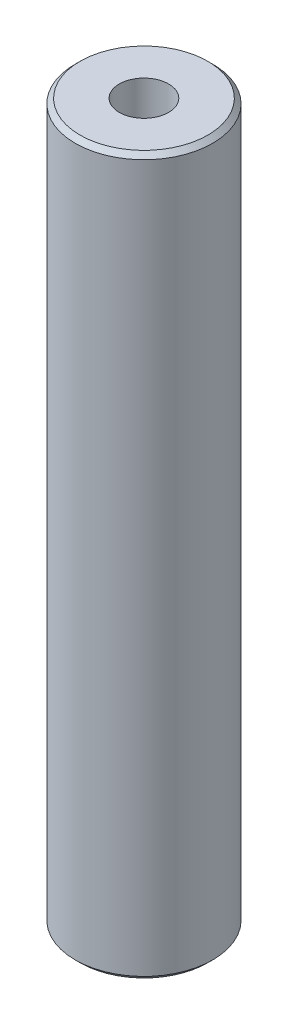
SolidWorks part; units mm, degrees
ref_plane "Front Plane" through (0, 0, 0) normal (0, 0, 1) x (1, 0, 0)
ref_plane "Top Plane" through (0, 0, 0) normal (0, 1, 0) x (1, 0, 0)
ref_plane "Right Plane" through (0, 0, 0) normal (1, 0, 0) x (0, 0, -1)
sketch "Sketch1" plane through (0, 0, 0) normal (0, 1, 0) x (1, 0, 0)
  circle A0 centre (0, 0) radius 57.5
  dimension "SHAFT_OD" = 115
extrude "Boss-Extrude1" add sketch "Sketch1" along normal blind 600
sketch "Sketch2" plane through (0, 0, 0) normal (0, 1, 0) x (1, 0, 0)
  circle A0 centre (0, 0) radius 20.654
  dimension "BORE_D" = 41.308
extrude "Cut-Extrude1" cut sketch "Sketch2" along normal through all
chamfer "Chamfer1" distance 3.9821 angle 45 2 edges at (0, 600, 57.5) (0, 0, 57.5)
